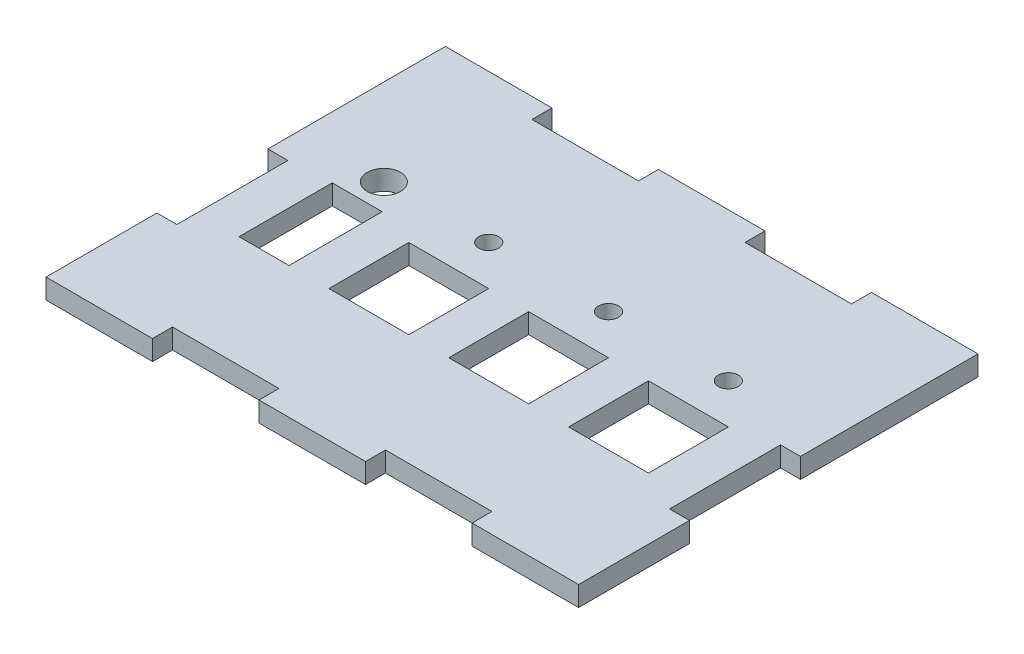
SolidWorks part; units mm, degrees
ref_plane "Front Plane" through (0, 0, 0) normal (0, 0, 1) x (1, 0, 0)
ref_plane "Top Plane" through (0, 0, 0) normal (0, 1, 0) x (1, 0, 0)
ref_plane "Right Plane" through (0, 0, 0) normal (1, 0, 0) x (0, 0, -1)
sketch "Top and Bottom" plane through (0, 0, 0) normal (0, 1, 0) x (1, 0, 0)
  line L0 (32, 60) -> (48, 60)
  line L1 (0, 0) -> (16, 0)
  line L2 (0, 0) -> (0, 16.6667)
  line L3 (0, 60) -> (16, 60)
  line L4 (80, 0) -> (80, 16.6667)
  line L5 (64, 60) -> (80, 60)
  line L6 (16, 60) -> (16, 57)
  line L7 (16, 57) -> (32, 57)
  line L8 (32, 60) -> (32, 57)
  line L9 (40.75, 31.75) -> (52.75, 31.75)
  line L10 (48, 60) -> (48, 57)
  line L11 (48, 57) -> (64, 57)
  line L12 (64, 60) -> (64, 57)
  line L13 (22.75, 31.75) -> (34.75, 31.75)
  line L14 (64, 0) -> (64, 3)
  line L15 (48, 3) -> (64, 3)
  line L16 (48, 0) -> (48, 3)
  line L17 (32, 0) -> (32, 3)
  line L18 (16, 0) -> (16, 3)
  line L19 (16, 3) -> (32, 3)
  line L20 (64, 0) -> (80, 0)
  line L21 (32, 0) -> (48, 0)
  line L22 (0, 33.3333) -> (0, 60)
  line L23 (0, 33.3333) -> (3, 33.3333)
  line L24 (80, 33.3333) -> (77, 33.3333)
  line L25 (0, 16.6667) -> (3, 16.6667)
  line L26 (3, 33.3333) -> (3, 16.6667)
  line L27 (77, 33.3333) -> (77, 16.6667)
  line L28 (80, 16.6667) -> (77, 16.6667)
  line L29 (80, 33.3333) -> (80, 60)
  line L30 (22.75, 31.75) -> (22.75, 19.75)
  line L31 (22.75, 19.75) -> (34.75, 19.75)
  line L32 (34.75, 31.75) -> (34.75, 19.75)
  line L33 (40.75, 31.75) -> (40.75, 19.75)
  line L34 (40.75, 19.75) -> (52.75, 19.75)
  line L35 (52.75, 31.75) -> (52.75, 19.75)
  line L36 (58.75, 31.75) -> (70.75, 31.75)
  line L37 (58.75, 31.75) -> (58.75, 19.75)
  line L38 (58.75, 19.75) -> (70.75, 19.75)
  line L39 (70.75, 31.75) -> (70.75, 19.75)
  line L41 (9.25, 33.75) -> (16.75, 33.75)
  line L42 (9.25, 33.75) -> (9.25, 19.75)
  line L43 (9.25, 19.75) -> (16.75, 19.75)
  line L44 (16.75, 33.75) -> (16.75, 19.75)
  circle A0 centre (28.75, 37.75) radius 1.5
  circle A1 centre (46.75, 37.75) radius 1.5
  circle A2 centre (64.75, 37.75) radius 1.5
  circle A3 centre (13, 37.75) radius 2.5
  dimension "D16" = 3
  dimension "D18" = 6
  dimension "D20" = 3
  dimension "D21" = 3
  dimension "D22" = 6
  dimension "D28" = 5
  dimension "D29" = 4
  dimension "D1" = 60
  dimension "D2" = 80
  dimension "D3" = 3
  dimension "D4" = 16
  dimension "D5" = 16
  dimension "D6" = 16
  dimension "D7" = 3
  dimension "D8" = 16
  dimension "D9" = 12
  dimension "D10" = 3
  dimension "D11" = 16.6667
  dimension "D12" = 16.6667
  dimension "D13" = 12
  dimension "D14" = 6
  dimension "D15" = 6
  dimension "D17" = 6
  dimension "D19" = 6
  dimension "D23" = 6
  dimension "D24" = 6
  dimension "D25" = 7.5
  dimension "D26" = 14
  dimension "D27" = 0
  dimension "D30" = 6
  dimension "D31" = 9.25
  dimension "D32" = 3.75
  dimension "D33" = 19.75
  dimension "D34" = 12
  dimension "D35" = 12
  dimension "D36" = 12
  dimension "D37" = 12
  dimension "D38" = 0
  dimension "D39" = 0
extrude "Top and Bottom Extruded" add sketch "Top and Bottom" along normal blind 3
